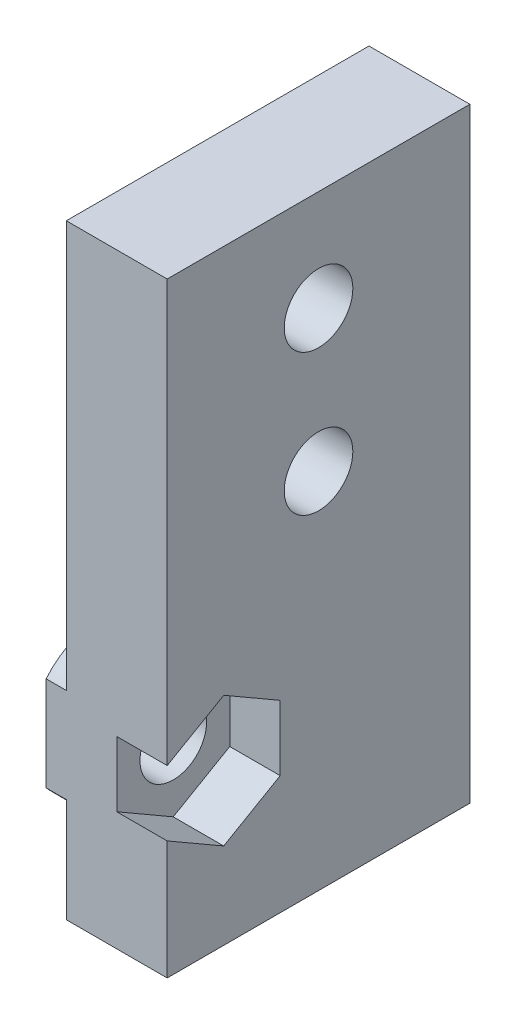
SolidWorks part; units mm, degrees
note: The reader was unsure of these and kept them because the rebuilt part matched: shared geometry of "Sketch1<3>".
ref_plane "Front" through (0, 0, 0) normal (0, 0, 1) x (1, 0, 0)
ref_plane "Top" through (0, 0, 0) normal (0, 1, 0) x (1, 0, 0)
ref_plane "Right" through (0, 0, 0) normal (1, 0, 0) x (0, 0, -1)
sketch "Sketch1" plane through (0, 0, 0) normal (1, 0, 0) x (0, 0, -1)
  line L1 (0, 0) -> (15, 0)
  line L2 (0, 0) -> (0, 30)
  line L3 (0, 30) -> (15, 30)
  line L4 (15, 0) -> (15, 30)
  line L6 (2.8, 4.2668) -> (5.6, 5.8834)
  line L7 (5.6, 5.8834) -> (5.6, 9.1166)
  line L8 (5.6, 9.1166) -> (2.8, 10.7332)
  line L9 (2.8, 10.7332) -> (0, 9.1166)
  line L10 (0, 9.1166) -> (0, 5.8834)
  line L11 (0, 5.8834) -> (2.8, 4.2668)
  circle A0 centre (7.5, 7.5) radius 1.6
  circle A1 centre (7.5, 20) radius 1.6
  circle A2 centre (2.8, 7.5) radius 2.8 construction
  circle A3 centre (7.5, 18) radius 1.7
  circle A4 centre (7.5, 25) radius 1.7
  circle A5 centre (2.8, 7.5) radius 1.65
  dimension "D3" = 7.5
  dimension "D7" = 25
  dimension "D8" = 18
  dimension "D1" = 30
  dimension "D2" = 15
  dimension "D4" = 20
  dimension "D5" = 2.8
  dimension "D6" = 7.5
extrude "Boss-Extrude1" add sketch "Sketch1" along normal blind 2.5
extrude "Boss-Extrude2" add sketch "Sketch1<3>" against normal blind 2.5
sketch "Sketch1<3>" plane through (0, 0, 0) normal (1, 0, 0) x (0, 0, -1) same geometry as "Sketch1"
sketch "Sketch4" plane through (-2.5, 0, 0) normal (-1, 0, 0) x (0, 0, 1)
  line L0 (0, 14.0191) -> (0, 3.2885)
  line L1 (0, 0) -> (0, 30) construction
  circle A0 centre (-2.8, 7.5) radius 1.65
  circle A1 centre (-2.8, 7.5) radius 3.65
  circle M7 centre (-2.8, 7.5) radius 1.65
  dimension "D1" = 2
extrude "Boss-Extrude3" add sketch "Sketch4" along normal blind 1 contours L0 A1 M7
